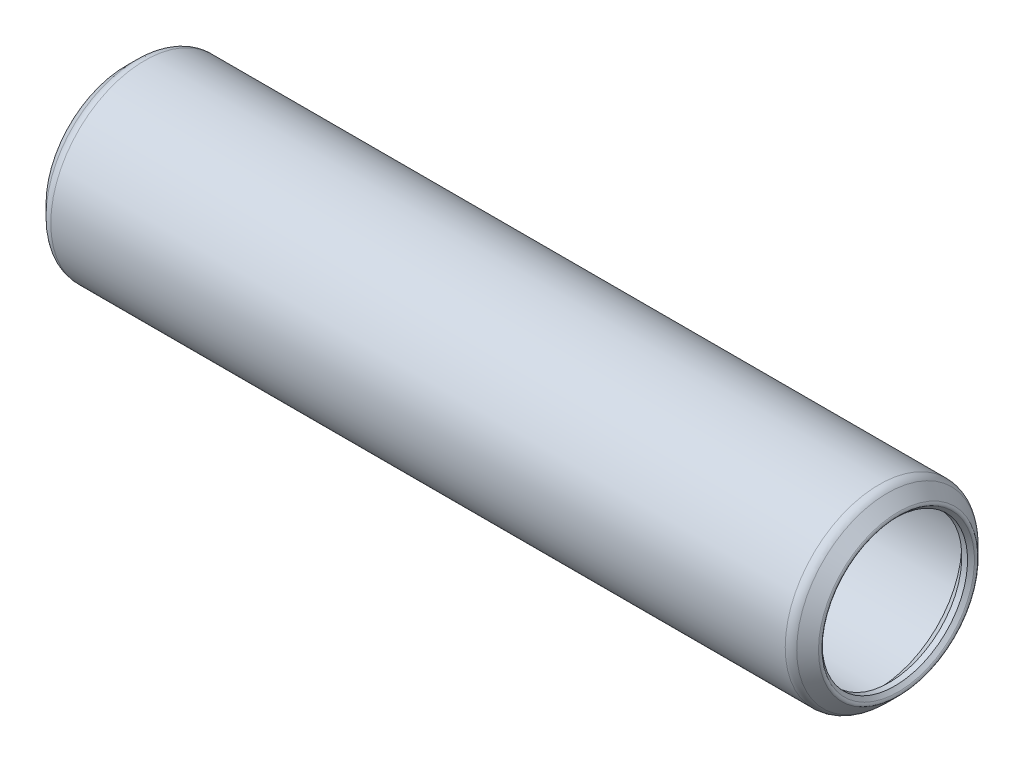
SolidWorks part; units mm, degrees
ref_plane "Front Plane" through (0, 0, 0) normal (0, 0, 1) x (1, 0, 0)
ref_plane "Top Plane" through (0, 0, 0) normal (0, 1, 0) x (1, 0, 0)
ref_plane "Right Plane" through (0, 0, 0) normal (1, 0, 0) x (0, 0, -1)
ref_plane "Plane1" through (36.5506, 0, 0) normal (1, 0, 0) x (0, 0, -1)
sketch "Sketch1" plane through (0, 0, 0) normal (0, 0, 1) x (1, 0, 0)
  line L0 (-0.445, 3.6899) -> (-0.2794, 3.5242)
  line L1 (-0.2794, 3.5242) -> (0, 3.5242)
  line L2 (0, 3.5242) -> (0.5588, 4.0831)
  line L3 (0.5588, 4.0831) -> (35.9918, 4.0831)
  line L4 (35.9918, 4.0831) -> (36.5506, 3.5242)
  line L5 (36.5506, 3.5242) -> (36.83, 3.5242)
  line L6 (36.83, 3.5242) -> (36.9956, 3.6899)
  line L7 (36.9956, 3.8695) -> (36.4695, 4.3956)
  line L8 (36.0744, 4.5593) -> (0.4763, 4.5593)
  line L9 (0.0811, 4.3956) -> (-0.445, 3.8695)
  line L10 (36.5506, 0) -> (0, 0) construction
  arc A0 (-0.445, 3.8695) -> (-0.445, 3.6899) centre (-0.3552, 3.7797) ccw
  arc A1 (36.9956, 3.6899) -> (36.9956, 3.8695) centre (36.9058, 3.7797) ccw
  arc A2 (36.4695, 4.3956) -> (36.0744, 4.5593) centre (36.0744, 4.0005) ccw
  arc A3 (0.4763, 4.5593) -> (0.0811, 4.3956) centre (0.4762, 4.0005) ccw
revolve "Revolve1" add sketch "Sketch1" angle 360 about L10 reverse direction yes
ref_plane "Plane2" through (18.2753, 0, 0) normal (1, 0, 0) x (0, 0, -1)
ref_plane "cp1 XY" through (18.2753, 0, 0) normal (1, 0, 0) x (0, 0, -1)
ref_plane "cp1 XZ" through (0, 4.5593, 0) normal (0, -1, 0) x (-1, 0, 0)
ref_plane "cp1 YZ" through (0, 0, 0) normal (0, 0, -1) x (-1, 0, 0)
ref_axis "cp1 X" through (18.2753, 4.5593, 80.9) along (0, 0, -1)
ref_axis "cp1 Y" through (18.2753, -50, 0) along (0, 1, 0)
ref_axis "cp1 Z" through (80.9, 4.5593, 0) along (-1, 0, 0)
sketch3d "cp1"
  point P0 (18.2753, 4.5593, 0)
ref_plane "cp2 XY" through (18.2753, 0, 0) normal (1, 0, 0) x (0, 0, -1)
ref_plane "cp2 XZ" through (0, 0, 0) normal (0, -1, 0) x (-1, 0, 0)
ref_plane "cp2 YZ" through (0, 0, -4.5593) normal (0, 0, -1) x (-1, 0, 0)
ref_axis "cp2 X" through (18.2753, 0, 80.9) along (0, 0, -1)
ref_axis "cp2 Y" through (18.2753, -50, -4.5593) along (0, 1, 0)
ref_axis "cp2 Z" through (80.9, 0, -4.5593) along (-1, 0, 0)
sketch3d "cp2"
  point P0 (18.2753, 0, -4.5593)
ref_plane "cp3 XY" through (18.2753, 0, 0) normal (1, 0, 0) x (0, 0, -1)
ref_plane "cp3 XZ" through (0, -4.5593, 0) normal (0, -1, 0) x (-1, 0, 0)
ref_plane "cp3 YZ" through (0, 0, 0) normal (0, 0, -1) x (-1, 0, 0)
ref_axis "cp3 X" through (18.2753, -4.5593, 80.9) along (0, 0, -1)
ref_axis "cp3 Y" through (18.2753, -50, 0) along (0, 1, 0)
ref_axis "cp3 Z" through (80.9, -4.5593, 0) along (-1, 0, 0)
sketch3d "cp3"
  point P0 (18.2753, -4.5593, 0)
ref_plane "cp4 XY" through (18.2753, 0, 0) normal (1, 0, 0) x (0, 0, -1)
ref_plane "cp4 XZ" through (0, 0, 0) normal (0, -1, 0) x (-1, 0, 0)
ref_plane "cp4 YZ" through (0, 0, 4.5593) normal (0, 0, -1) x (-1, 0, 0)
ref_axis "cp4 X" through (18.2753, 0, 80.9) along (0, 0, -1)
ref_axis "cp4 Y" through (18.2753, -50, 4.5593) along (0, 1, 0)
ref_axis "cp4 Z" through (80.9, 0, 4.5593) along (-1, 0, 0)
sketch3d "cp4"
  point P0 (18.2753, 0, 4.5593)
ref_plane "tube_front XY" through (0, 0, 0) normal (1, 0, 0) x (0, 0, -1)
ref_plane "tube_front XZ" through (0, 0, 0) normal (0, -1, 0) x (-1, 0, 0)
ref_plane "tube_front YZ" through (0, 0, 0) normal (0, 0, -1) x (-1, 0, 0)
ref_axis "tube_front X" through (0, 0, 80.9) along (0, 0, -1)
ref_axis "tube_front Y" through (0, -50, 0) along (0, 1, 0)
ref_axis "tube_front Z" through (80.9, 0, 0) along (-1, 0, 0)
sketch3d "tube_front"
  point P0 (0, 0, 0)
ref_plane "tube_rear XY" through (36.5506, 0, 0) normal (1, 0, 0) x (0, 0, -1)
ref_plane "tube_rear XZ" through (0, 0, 0) normal (0, -1, 0) x (-1, 0, 0)
ref_plane "tube_rear YZ" through (0, 0, 0) normal (0, 0, -1) x (-1, 0, 0)
ref_axis "tube_rear X" through (36.5506, 0, 80.9) along (0, 0, -1)
ref_axis "tube_rear Y" through (36.5506, -50, 0) along (0, 1, 0)
ref_axis "tube_rear Z" through (80.9, 0, 0) along (-1, 0, 0)
sketch3d "tube_rear"
  point P0 (36.5506, 0, 0)
